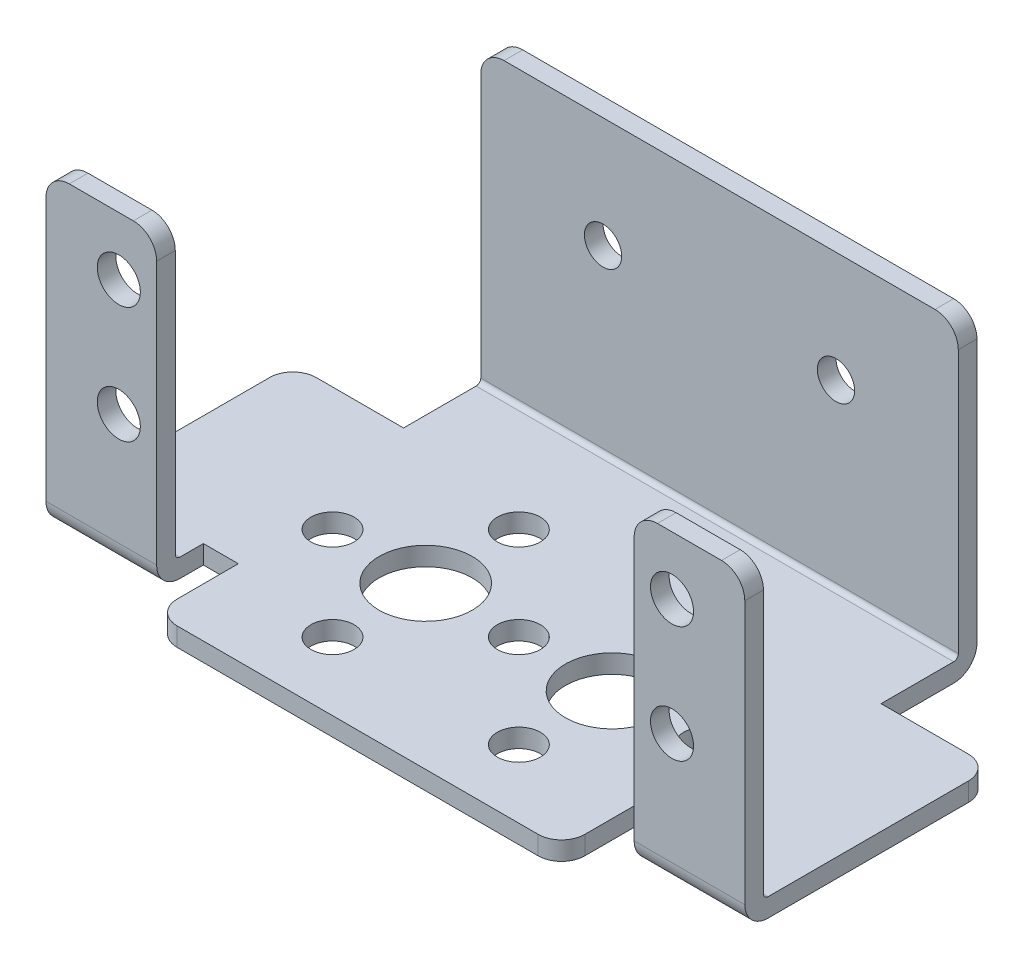
SolidWorks part; units mm, degrees
material "5052 Alloy"
ref_plane "Front Plane" through (0, 0, 0) normal (0, 0, 1) x (1, 0, 0)
ref_plane "Top Plane" through (0, 0, 0) normal (0, 1, 0) x (1, 0, 0)
ref_plane "Right Plane" through (0, 0, 0) normal (1, 0, 0) x (0, 0, -1)
sketch "Sketch1" plane through (0, 0, 0) normal (0, 1, 0) x (1, 0, 0)
  line L0 (-30, -10.6) -> (-30, 10.6)
  line L1 (-30, 10.6) -> (-20.5, 10.6)
  line L2 (-20.5, 10.6) -> (-20.5, 18.8307)
  line L3 (-20.5, 18.8307) -> (20.5, 18.8307)
  line L4 (20.5, 18.8307) -> (20.5, 10.6)
  line L5 (20.5, 10.6) -> (30, 10.6)
  line L6 (30, 10.6) -> (30, -10.6)
  line L7 (30, -10.6) -> (20.5, -10.6)
  line L8 (20.5, -10.6) -> (20.5, -6.588)
  line L9 (20.5, -6.588) -> (17.5, -6.588)
  line L10 (17.5, -6.588) -> (17.5, -13.8389)
  line L11 (17.5, -13.8389) -> (-17.5, -13.8389)
  line L12 (-17.5, -13.8389) -> (-17.5, -6.588)
  line L13 (-17.5, -6.588) -> (-20.5, -6.588)
  line L14 (-20.5, -6.588) -> (-20.5, -10.6)
  line L15 (-20.5, -10.6) -> (-30, -10.6)
  line L16 (-30, 0) -> (30, 0) construction
  line L17 (0, 18.8307) -> (0, -13.8389) construction
  dimension "D1" = 21.2
  dimension "D2" = 9.5
  dimension "D3" = 41
  dimension "D4" = 6.588
  dimension "D5" = 13.8389
  dimension "D6" = 9.5
  dimension "D8" = 35
  dimension "D9" = 3
  dimension "D11" = 29.4307
extrude "Extrude1" add sketch "Sketch1" along normal blind 1.6
sketch "Sketch2" plane through (0, 1.6, 0) normal (0, 1, 0) x (1, 0, 0)
  line L0 (-20.5, -10.6) -> (-20.5, -6.588) construction
  line L1 (-30, -10.6) -> (-20.5, -10.6)
  line L2 (-30, -10.6) -> (-30, -9)
  line L3 (-30, -9) -> (-20.5, -9)
  line L4 (-20.5, -10.6) -> (-20.5, -9)
  line L5 (30, -10.6) -> (30, 10.6) construction
  line L6 (20.5, -10.6) -> (30, -10.6)
  line L7 (20.5, -10.6) -> (20.5, -9)
  line L8 (20.5, -9) -> (30, -9)
  line L9 (30, -10.6) -> (30, -9)
  line L10 (20.5, 10.6) -> (20.5, 18.8307) construction
  line L11 (-20.5, 18.8307) -> (20.5, 18.8307)
  line L12 (-20.5, 18.8307) -> (-20.5, 17.2307)
  line L13 (-20.5, 17.2307) -> (20.5, 17.2307)
  line L14 (20.5, 18.8307) -> (20.5, 17.2307)
  dimension "D1" = 1.6
  dimension "D2" = 1.6
  dimension "D3" = 1.6
extrude "Extrude2" add sketch "Sketch2" along normal blind 25
fillet "Fillet2" radius 0.4 3 edges at (25.25, 1.6, 9) (0, 1.6, -17.2307)
fillet "Fillet3" radius 2 13 edges at (-30, 0.8, -10.6) (-17.5, 0.8, 13.8389) (30, 0.8, -10.6) (20.5, 26.6, 9.8) (30, 26.6, 9.8) (20.5, 26.6, -18.0307) (-20.5, 26.6, -18.0307) (-30, 26.6, 9.8) (-20.5, 26.6, 9.8) (-25.25, 0, 10.6) (25.25, 0, 10.6) (0, 0, -18.8307) (17.5, 0.8, 13.8389)
sketch "Sketch3" plane through (0, 0, 10.6) normal (0, 0, 1) x (1, 0, 0)
  line L0 (-30, 0) -> (-20.5, 0) construction
  line L3 (-23.75, 11.6) -> (23.75, 11.6) construction
  line L4 (23.75, 21.6) -> (-23.75, 21.6) construction
  line L5 (0, 11.6) -> (0, 21.6) construction
  circle A0 centre (-23.75, 21.6) radius 1.85
  circle A1 centre (-23.75, 11.6) radius 1.85
  circle A2 centre (23.75, 21.6) radius 1.85
  circle A3 centre (23.75, 11.6) radius 1.85
  dimension "D1" = 23.75
  dimension "D2" = 3.7
  dimension "D5" = 11.6
  dimension "D8" = 10
hole_wizard "Ø3.7 (3.7) Diameter Hole1" positions "Sketch7" profile "Sketch6" hole size "Ø3.7" standard "Ansi Metric" end condition through all
sketch "Sketch7" plane through (0, 0, 10.6) normal (0, 0, 1) x (1, 0, 0)
  point P0 (-23.75, 21.6)
  point P1 (-23.75, 11.6)
  point P4 (23.75, 11.6)
  point P7 (23.75, 21.6)
sketch "Sketch6" plane through (-23.75, 21.6, 10.6) normal (1, 0, 0) x (0, -1, 0)
  line L0 (0, 0) -> (0, 29.4307)
  line L1 (0, 29.4307) -> (1.85, 29.4307)
  line L2 (1.85, 29.4307) -> (1.85, 0)
  line L5 (1.85, 0) -> (0, 0)
  line L11 (0, -6.35) -> (0, 107.95) construction
  dimension "Thru Hole Dia." = 3.7
  dimension "Thru Hole Depth" = 29.4307
sketch "Sketch4" plane through (0, 0, -17.2307) normal (0, 0, 1) x (1, 0, 0)
  line L0 (0, 0) -> (0, 17.0945) construction
  line L1 (-10, 17.0945) -> (10, 17.0945) construction
  line L2 (-15.5, 0) -> (15.5, 0) construction
  circle A0 centre (10, 17.0945) radius 1.6
  circle A1 centre (-10, 17.0945) radius 1.6
  dimension "D2" = 3.2
  dimension "D1" = 10
  dimension "D3" = 17.0945
extrude "Cut-Extrude2" cut sketch "Sketch4" against normal through all
sketch "Sketch5" plane through (0, 1.6, 0) normal (0, 1, 0) x (1, 0, 0)
  line L2 (-8, 0) -> (8, 0) construction
  point P3 (0, 0)
  line B0 (8, 0) -> (8, 8) construction
  circle B1 centre (8, 0) radius 4
  circle B2 centre (8, 8) radius 1.85
  circle B3 centre (8, 0) radius 8 construction
  line B4 (-8, 0) -> (-8, 8) construction
  circle B5 centre (-8, 0) radius 4
  circle B6 centre (-8, 8) radius 1.85
  circle B7 centre (-8, 0) radius 8 construction
  dimension "D1" = 16
sketch_block_instance "Block-Tetrix Hole Pattern - 8x8x3.7-1"
sketch_block "Block-Tetrix Hole Pattern - 8x8x3.7" parameters "D1"=3.7, "D2"=8, "D3"=16
sketch_block_instance "Block-Tetrix Hole Pattern - 8x8x3.7-3" parameters "D1"=22.4652, "D2"=19.6
extrude "Cut-Extrude3" cut sketch "Sketch5" against normal through all contours B1 | B5 region at (8, 1.6, 0) region at (-8, 1.6, 0)
extrude "Cut-Extrude4" cut sketch "Sketch5<3>" against normal through all contours B2 region at (8, 1.6, -8)
sketch "Sketch5<3>" plane through (0, 1.6, 0) normal (0, 1, 0) x (1, 0, 0) same geometry as "Sketch5"
pattern_circular "CirPattern1" count 4 over 360 about axis through (8, 0, 0) along (0, 1, 0) of "Cut-Extrude4"
extrude "Cut-Extrude5" cut sketch "Sketch5<4>" against normal blind 10 contours B6 region at (-8, 1.6, -8)
sketch "Sketch5<4>" plane through (0, 1.6, 0) normal (0, 1, 0) x (1, 0, 0) same geometry as "Sketch5"
pattern_circular "CirPattern2" count 4 over 360 about axis through (-8, 0, 0) along (0, 1, 0) of "Cut-Extrude5"
